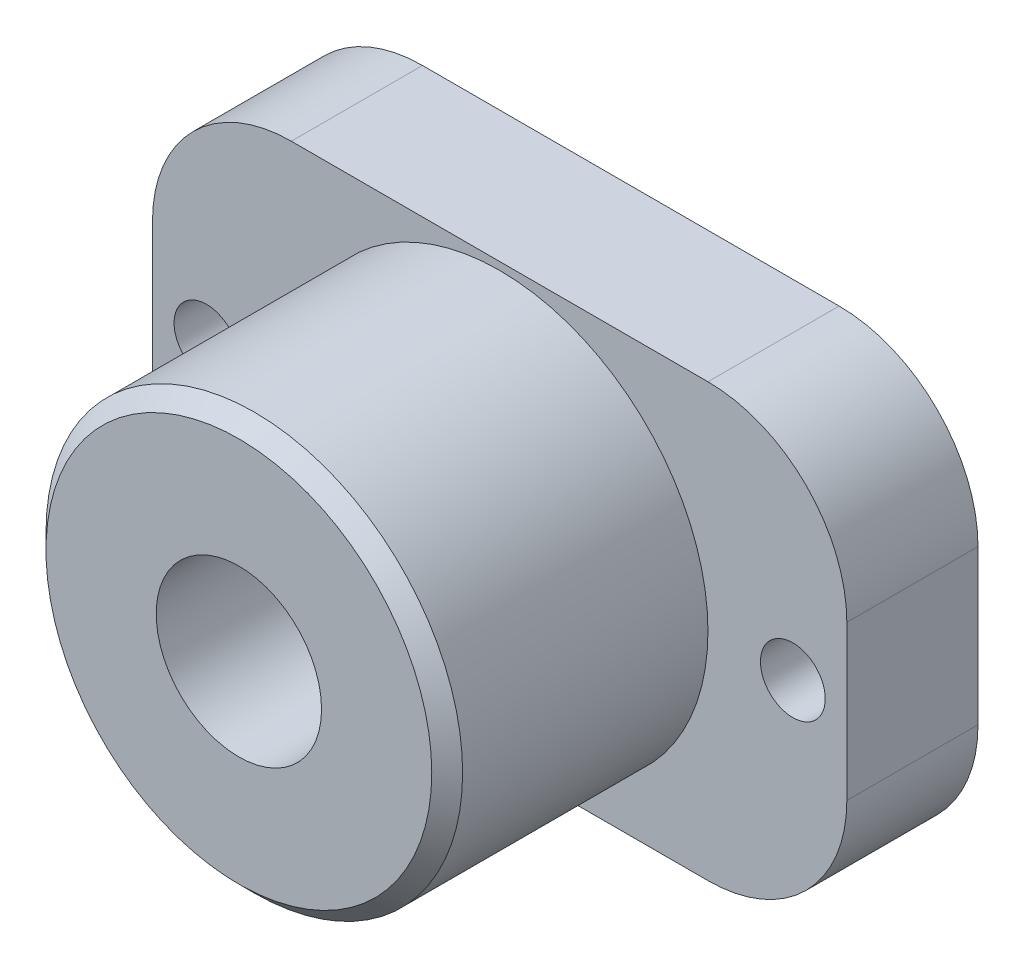
SolidWorks part; units mm, degrees
material "Delrin 150"
ref_plane "Front Plane" through (0, 0, 0) normal (0, 0, 1) x (1, 0, 0)
ref_plane "Top Plane" through (0, 0, 0) normal (0, 1, 0) x (1, 0, 0)
ref_plane "Right Plane" through (0, 0, 0) normal (1, 0, 0) x (0, 0, -1)
ref_axis "Axis1" through (0, 0, -88.99) along (0, 0, 1)
ref_axis "Axis2" through (0, -55, 0) along (0, 1, 0)
ref_axis "Axis3" through (-88.99, 0, 0) along (1, 0, 0)
sketch "Sketch2" plane through (0, 0, 0) normal (1, 0, 0) x (0, 0, -1)
  line L0 (0, 13.5) -> (16.9, 13.5)
  line L1 (16.9, 13.5) -> (16.9, 14)
  line L2 (16.9, 14) -> (25.4, 14)
  line L3 (25.4, 14) -> (25.4, 0)
  line L4 (25.4, 0) -> (0, 0)
  line L5 (0, 0) -> (0, 13.5)
  line L6 (0, 0) -> (-32.6946, 0) construction
  dimension "D1" = 27
  dimension "D2" = 0.5
  dimension "D3" = 8.5
  dimension "D4" = 25.4
revolve "Revolve1" add sketch "Sketch2" angle 360 about L6
hole_wizard "1/2-13 Tapped Hole1" positions "Sketch4" profile "Sketch5" tap size "1/2-13" standard "ANSI Inch" end condition through all
sketch "Sketch4" plane through (0, 0, 0) normal (0, 0, 1) x (1, 0, 0)
  point P0 (0, 0)
sketch "Sketch5" plane through (0, 0, 0) normal (1, 0, 0) x (0, -1, 0)
  line L0 (0, 0) -> (0, 25.4)
  line L1 (0, 25.4) -> (5.3581, 25.4)
  line L2 (5.3581, 25.4) -> (5.3581, 0)
  line L5 (5.3581, 0) -> (0, 0)
  line L11 (0, -6.35) -> (0, 107.95) construction
  dimension "Thread Major Dia." = 10.7163
  dimension "Thru Tap Drill Depth" = 25.4
sketch "Sketch9" plane through (0, 0, -16.9) normal (0, 0, 1) x (1, 0, 0)
  line L0 (0, 0) -> (0, 14) construction
  line L1 (22.5, -14) -> (-22.5, -14)
  line L2 (22.5, -14) -> (22.5, 14)
  line L3 (22.5, 14) -> (-22.5, 14)
  line L4 (-22.5, -14) -> (-22.5, 14)
  line L5 (22.5, -14) -> (-22.5, 14) construction
  line L6 (22.5, 14) -> (-22.5, -14) construction
  circle A0 centre (0, 0) radius 14 construction
  circle A1 centre (0, 0) radius 13.5 construction
  circle A2 centre (0, 0) radius 13.5
  point P0 (0, 0)
  dimension "D1" = 45
extrude "Boss-Extrude1" add sketch "Sketch9" against normal up to surface (8.5 mm away) up to face at (5.3581, 0, -25.4)
hole_wizard "Tap Drill for M5x0.8 Tap1" positions "Sketch7" profile "Sketch6" hole size "M5x0.8" standard "ANSI Metric" end condition through all
sketch "Sketch7" plane through (0, 0, -16.9) normal (0, 0, 1) x (1, 0, 0)
  line L0 (0, 0) -> (0, 14) construction
  line L3 (0, 0) -> (-22.5, 0) construction
  line L4 (-22.5, 14) -> (-22.5, -14) construction
  line L6 (22.5, 14) -> (-22.5, 14) construction
  point P0 (-19, 0)
  point P32 (19, 0)
  dimension "D1" = 38
sketch "Sketch6" plane through (-19, 0, -16.9) normal (1, 0, 0) x (0, -1, 0)
  line L0 (0, 0) -> (0, 8.5)
  line L1 (0, 8.5) -> (2.1, 8.5)
  line L2 (2.1, 8.5) -> (2.1, 0)
  line L5 (2.1, 0) -> (0, 0)
  line L11 (0, -6.35) -> (0, 107.95) construction
  dimension "Thru Hole Dia." = 4.2
  dimension "Thru Hole Depth" = 8.5
fillet "Fillet1" radius 9 4 edges at (-22.5, 14, -21.15) (22.5, -14, -21.15) (22.5, 14, -21.15) (-22.5, -14, -21.15)
chamfer "Chamfer1" distance 1 angle 45 1 edges at (-13.5, 0, 0)
sketch "Sketch8" plane through (0, 0, -25.4) normal (0, 0, -1) x (-1, 0, 0)
  circle A0 centre (0, 0) radius 11.5
  dimension "D1" = 23
extrude "Cut-Extrude2" cut sketch "Sketch8" against normal blind 12
